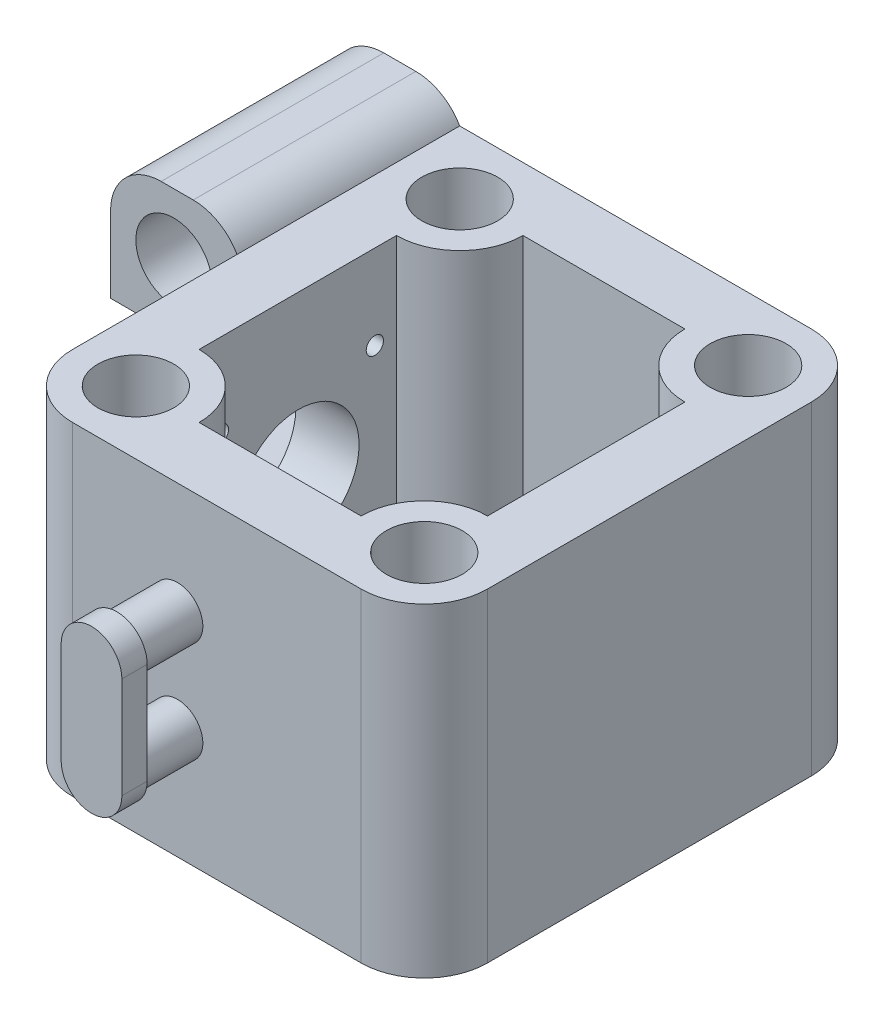
SolidWorks part; units mm, degrees
ref_plane "Front Plane" through (0, 0, 0) normal (0, 0, 1) x (1, 0, 0)
ref_plane "Top Plane" through (0, 0, 0) normal (0, 1, 0) x (1, 0, 0)
ref_plane "Right Plane" through (0, 0, 0) normal (1, 0, 0) x (0, 0, -1)
sketch "Sketch2" plane through (0, 0, 0) normal (0, 1, 0) x (1, 0, 0)
  line L1 (-28.5, 32) -> (28.5, 32)
  line L2 (-28.5, 32) -> (-28.5, -32)
  line L3 (-28.5, -32) -> (28.5, -32)
  line L4 (28.5, 32) -> (28.5, -32)
  line L5 (-28.5, 32) -> (28.5, -32) construction
  line L6 (-28.5, -32) -> (28.5, 32) construction
  line L7 (-41, 44.5) -> (28.5, 44.5)
  line L8 (-41, 44.5) -> (-41, -32)
  line L9 (-28.5, -44.5) -> (28.5, -44.5)
  line L10 (41, 32) -> (41, -32)
  line L11 (-37.4966, 40.6782) -> (37.4966, -40.6782) construction
  line L12 (-37.4966, -40.6782) -> (37.4966, 40.6782) construction
  circle A0 centre (-28.5, 32) radius 12.5
  circle A1 centre (28.5, 32) radius 12.5
  circle A2 centre (28.5, -32) radius 12.5
  circle A3 centre (-28.5, -32) radius 12.5
  circle A4 centre (-28.5, 32) radius 7.5
  circle A5 centre (28.5, 32) radius 7.5
  circle A6 centre (-28.5, -32) radius 7.5
  circle A7 centre (28.5, -32) radius 7.5
  point P0 (0, 0)
  point P32 (0, 0)
  dimension "D3" = 25
  dimension "D4" = 15
  dimension "D1" = 64
  dimension "D2" = 57
extrude "Boss-Extrude1" add sketch "Sketch2" along normal blind 64 contours A1 L7 A0 L1 | A3 L2 A0 L8 | A3 L9 A2 L3 | A2 L10 A1 L4 | A5 L1 A1 L4 | A5 L4 A1 L1 | A4 L2 A0 L1 | A4 L1 A0 L2 | A6 L2 A3 L3 | A6 L3 A3 L2 | A7 L3 A2 L4 | A7 L4 A2 L3 | A0 L7 L8 region at (-34.0533, 0, -37.5533) region at (-22.0012, 0, -25.5012) region at (0, 0, -38.7465) region at (-35.1682, 0, 0) region at (19.9112, 0, -40.5888) region at (22.0012, 0, -25.5012) region at (-38.2079, 0, -41.7079) region at (-22.0012, 0, 25.5012) region at (-28.8536, 0, 22) region at (35.1682, 0, 0) region at (0, 0, 38.7465) region at (37.0888, 0, 23.4112) region at (22.0012, 0, 25.5012)
sketch "Sketch3" plane through (-28.5, 0, 0) normal (1, 0, 0) x (0, 0, -1)
  line L3 (-19.5, 10) -> (-21.6931, 10)
  line L4 (24.5, 54) -> (24.5, 53.91)
  line L5 (19.5, 0) -> (-19.5, 0) construction
  line L6 (44.5, 64) -> (44.5, 0) construction
  line L7 (-21.9574, 53.9545) -> (23.2476, 11.2315) construction
  line L8 (23.3128, 52.7814) -> (-21.9691, 9.7377) construction
  line L9 (24.5, 10.0478) -> (24.5, 10)
  line L10 (-15.5594, 47.4496) -> (15.4406, 47.4496)
  line L11 (-15.5594, 47.4496) -> (-15.5594, 16.4496)
  line L12 (-15.5594, 16.4496) -> (15.4406, 16.4496)
  line L13 (15.4406, 47.4496) -> (15.4406, 16.4496)
  line L14 (-15.5594, 47.4496) -> (15.4406, 16.4496) construction
  line L15 (-15.5594, 16.4496) -> (15.4406, 47.4496) construction
  circle A0 centre (0.1168, 31.9123) radius 12
  point P16 (-0.0594, 31.9496)
  dimension "D6" = 24
  dimension "D1" = 44
  dimension "D2" = 31
  dimension "D4" = 10
  dimension "D5" = 20
extrude "Cut-Extrude3" cut sketch "Sketch3" against normal up to next contours A0 region at (-28.5, 31.9123, -0.1168)
sketch "Sketch4" plane through (-41, 0, 0) normal (-1, 0, 0) x (0, 0, 1)
  line L0 (-44.5, 64) -> (-44.5, 0) construction
  line L1 (-44.5, 69) -> (-0.5, 69)
  line L2 (-44.5, 69) -> (-44.5, 44)
  line L3 (-44.5, 44) -> (-0.5, 44)
  line L4 (-0.5, 69) -> (-0.5, 44)
  line L5 (-44.5, -5) -> (-0.5, -5)
  line L6 (-44.5, -5) -> (-44.5, 20)
  line L7 (-44.5, 20) -> (-0.5, 20)
  line L8 (-0.5, -5) -> (-0.5, 20)
  line L9 (-44.5, 0) -> (32, 0) construction
  dimension "D1" = 25
  dimension "D2" = 25
  dimension "D3" = 44
  dimension "D4" = 44
  dimension "D5" = 0
  dimension "D6" = 5
  dimension "D7" = 24
  dimension "D8" = 0
extrude "Boss-Extrude2" add sketch "Sketch4" along normal blind 25
sketch "Sketch5" plane through (-66, 0, 0) normal (-1, 0, 0) x (0, 0, 1)
  line L1 (-41.8773, 44.0002) -> (-21.8773, 44.0002)
  line L2 (-41.8773, 44.0002) -> (-41.8773, 19.9998)
  line L3 (-41.8773, 19.9998) -> (-21.8773, 19.9998)
  line L4 (-21.8773, 44.0002) -> (-21.8773, 19.9998)
  dimension "D1" = 20
  dimension "D2" = 24.0005
extrude "Boss-Extrude3" add sketch "Sketch5" against normal blind 3
sketch "Sketch6" plane through (0, 0, -0.5) normal (0, 0, 1) x (1, 0, 0)
  line L5 (-41, 44) -> (-41, 64) construction
  line L6 (-41, 0) -> (-41, 19.9184) construction
  line L7 (-66, 69) -> (-41, 69) construction
  line L8 (-66, -5) -> (-41, -5) construction
  circle A0 centre (-53.5, 56.5) radius 7.5
  circle A1 centre (-53.5, 7.5) radius 7.5
  dimension "D3" = 12.5
  dimension "D6" = 49
  dimension "D4" = 15
  dimension "D7" = 15
  dimension "D1" = 12.5
  dimension "D2" = 12.5
  dimension "D5" = 12.5
extrude "Cut-Extrude4" cut sketch "Sketch6" against normal up to next
fillet "Fillet1" radius 10 2 edges at (-66, -5, -22.5) (-66, 69, -22.5)
sketch "Sketch7" plane through (0, 0, 44.5) normal (0, 0, 1) x (1, 0, 0)
  line L0 (-28.2107, 63.9652) -> (28.6418, -0.1907) construction
  line L1 (28.6418, -0.1907) -> (28.571, 64.1127) construction
  line L2 (28.571, 64.1127) -> (-28.3582, -0.1907) construction
  line L3 (-28.3582, -0.1907) -> (-28.2107, 63.9652) construction
  line L4 (-7.7612, 63.9836) -> (-7.7612, -0.0248)
  circle A0 centre (-7.7612, 41.9794) radius 5
  circle A1 centre (-7.7612, 21.9794) radius 5
  point P8 (-7.7612, 31.9794)
  dimension "D3" = 10
  dimension "D4" = 10
  dimension "D1" = 10
  dimension "D2" = 10
  dimension "D5" = 20.5
  dimension "D6" = 57
extrude "Boss-Extrude4" add sketch "Sketch7" along normal blind 12 contours L4 A0 | L4 A0 | L4 A1 | L4 A1 region at (-5.6391, 41.9794, 44.5) region at (-5.6391, 21.9794, 44.5) region at (-9.8832, 21.9794, 44.5) region at (-9.8832, 41.9794, 44.5)
sketch "Sketch8" plane through (-66, 0, 0) normal (-1, 0, 0) x (0, 0, 1)
  line L0 (-41.9733, 43.7709) -> (-21.9682, 20.008) construction
  line L1 (-21.9682, 20.008) -> (-21.7471, 43.992) construction
  line L2 (-21.7471, 43.992) -> (-41.9733, 20.2291) construction
hole_wizard "CSK for M3 Countersunk Flat Head Screw1" positions "Sketch9" profile "Sketch10" countersink size "M3" standard "DIN"
sketch "Sketch9" plane through (-66, 0, 0) normal (-1, 0, 0) x (0, 0, 1)
  point P0 (-32.026, 32.0553)
sketch "Sketch10" plane through (-66, 32.0553, -32.026) normal (0, 1, 0) x (0, 0, 1)
  line L0 (0, 0) -> (0, 31.0215)
  line L1 (0, 31.0215) -> (1.7, 30)
  line L2 (1.7, 30) -> (1.7, 1.45)
  line L3 (1.7, 1.45) -> (3.15, 0)
  line L5 (3.15, 0) -> (0, 0)
  line L6 (-1.7, 1.45) -> (-3.15, 0) construction
  line L10 (0, 31.0215) -> (-1.7, 30) construction
  line L11 (0, -6.35) -> (0, 107.95) construction
  dimension "Hole Dia." = 3.4
  dimension "Hole Depth" = 30
  dimension "Near C'Sink Dia." = 6.3
  dimension "Near C'Sink Angle" = 90
  dimension "Drill Angle" = 118
sketch "Sketch11" plane through (-28.5, 0, 0) normal (1, 0, 0) x (0, 0, -1)
  line L1 (-13, 47.5) -> (18, 47.5)
  line L2 (-13, 47.5) -> (-13, 16.5)
  line L3 (-13, 16.5) -> (18, 16.5)
  line L4 (18, 47.5) -> (18, 16.5)
  line L5 (-19.5, 64) -> (-19.5, 0) construction
  line L6 (19.5, 64) -> (-19.5, 64) construction
  dimension "D1" = 6.5
  dimension "D2" = 31
  dimension "D3" = 31
  dimension "D4" = 16.5
hole_wizard "CSK for M3 Countersunk Flat Head Screw4" positions "Sketch16" profile "Sketch18" countersink size "M3" standard "DIN"
sketch "Sketch16" plane through (-41, 0, 0) normal (-1, 0, 0) x (0, 0, 1)
  point P0 (-15.2261, 47.3078)
  point P2 (15.3894, 47.4183)
  point P4 (15.3894, 16.6922)
  point P6 (-15.5577, 16.4712)
sketch "Sketch18" plane through (-41, 47.3078, -15.2261) normal (0, 1, 0) x (0, 0, 1)
  line L0 (0, 0) -> (0, 21.0215)
  line L1 (0, 21.0215) -> (1.7, 20)
  line L2 (1.7, 20) -> (1.7, 1.45)
  line L3 (1.7, 1.45) -> (3.15, 0)
  line L5 (3.15, 0) -> (0, 0)
  line L6 (-1.7, 1.45) -> (-3.15, 0) construction
  line L10 (0, 21.0215) -> (-1.7, 20) construction
  line L11 (0, -6.35) -> (0, 107.95) construction
  dimension "Hole Dia." = 3.4
  dimension "Hole Depth" = 20
  dimension "Near C'Sink Dia." = 6.3
  dimension "Near C'Sink Angle" = 90
  dimension "Drill Angle" = 118
sketch "Sketch19" plane through (-66, 0, 0) normal (-1, 0, 0) x (0, 0, 1)
  circle A0 centre (-15.2261, 47.4183) radius 2.5
  circle A1 centre (-15.3367, 16.2501) radius 2.5
  dimension "D1" = 5
extrude "Cut-Extrude5" cut sketch "Sketch19" against normal blind 30
sketch "Sketch20" plane through (0, 0, 56.5) normal (0, 0, 1) x (1, 0, 0)
  line L0 (-7.7612, 41.9794) -> (-7.7612, 21.9794) construction
  line L1 (-1.7612, 41.9794) -> (-1.7612, 21.9794)
  line L2 (-13.7612, 41.9794) -> (-13.7612, 21.9794)
  arc A0 (-1.7612, 41.9794) -> (-13.7612, 41.9794) centre (-7.7612, 41.9794) ccw
  arc A1 (-13.7612, 21.9794) -> (-1.7612, 21.9794) centre (-7.7612, 21.9794) ccw
  circle A2 centre (-7.7612, 41.9794) radius 5 construction
  circle A3 centre (-7.7612, 21.9794) radius 5 construction
  point P2 (-7.7612, 31.9794)
  dimension "D1" = 0
  dimension "D2" = 0
  dimension "D3" = 12
extrude "Boss-Extrude5" add sketch "Sketch20" along normal blind 5
fillet "Fillet2" radius 10 2 edges at (-41, -5, -22.5) (-41, 69, -22.5)
